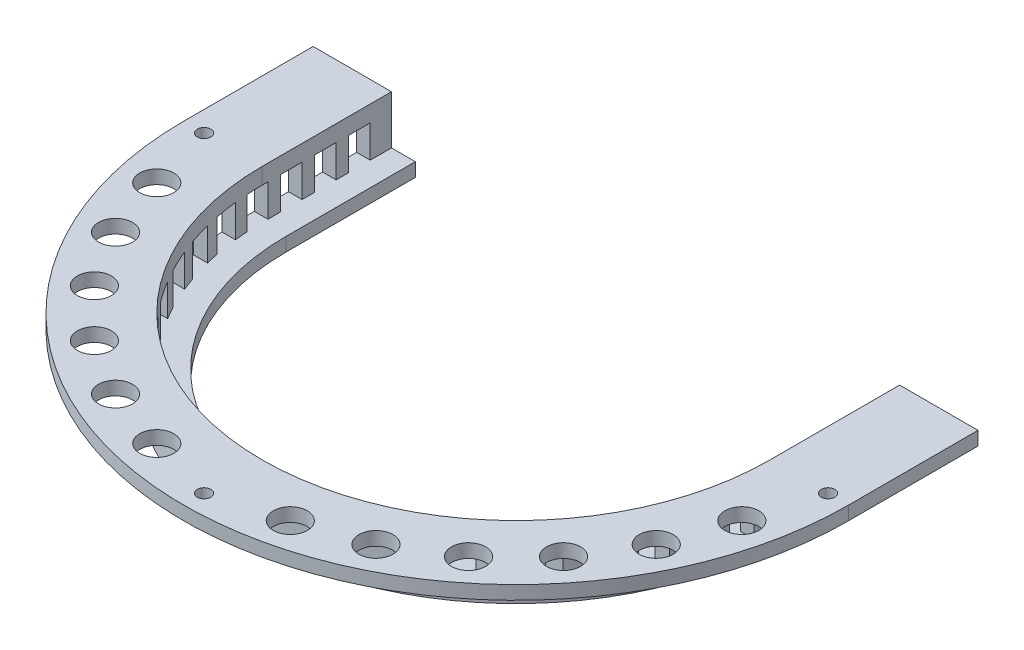
SolidWorks part; units mm, degrees
ref_plane "Front Plane" through (0, 0, 0) normal (0, 0, 1) x (1, 0, 0)
ref_plane "Top Plane" through (0, 0, 0) normal (0, 1, 0) x (1, 0, 0)
ref_plane "Right Plane" through (0, 0, 0) normal (1, 0, 0) x (0, 0, -1)
sketch "Sketch1" plane through (0, 0, 0) normal (0, 0, 1) x (1, 0, 0)
  line L0 (0, 0) -> (-74.5518, 0) construction
  line L1 (-74.5518, 0) -> (-74.5518, 14.28)
  line L2 (-74.5518, 0) -> (-67.5518, 0)
  line L3 (-67.5518, 0) -> (-67.5518, -4)
  line L4 (-67.5518, -4) -> (-78.5518, -4)
  line L5 (-78.5518, -4) -> (-78.5518, 10.28)
  line L6 (-78.5518, 14.28) -> (-74.5518, 14.28)
  line L7 (-78.5518, 14.28) -> (-97.5518, 14.28)
  line L8 (-97.5518, 14.28) -> (-97.5518, 10.28)
  line L9 (-97.5518, 10.28) -> (-78.5518, 10.28)
  line L10 (0, 0) -> (0, 25.527) construction
  dimension "D1" = 14.28
  dimension "D2" = 7
  dimension "D3" = 4
  dimension "D4" = 11
  dimension "D5" = 19
  dimension "D6" = 4
revolve "Revolve1" add sketch "Sketch1" angle 180 about L10
sketch "Sketch3" plane through (0, 0, 0) normal (0, 0, -1) x (-1, 0, 0)
  line L0 (-97.5518, 14.28) -> (-74.5518, 14.28)
  line L1 (-74.5518, 14.28) -> (-74.5518, 0)
  line L2 (-74.5518, 0) -> (-67.5518, 0)
  line L3 (-67.5518, 0) -> (-67.5518, -4)
  line L4 (-67.5518, -4) -> (-78.5518, -4)
  line L5 (-78.5518, -4) -> (-78.5518, 10.28)
  line L6 (-78.5518, 10.28) -> (-97.5518, 10.28)
  line L7 (-97.5518, 10.28) -> (-97.5518, 14.28)
extrude "Boss-Extrude1" add sketch "Sketch3" along normal blind 38
extrude "Boss-Extrude2" add sketch "Sketch1<2>" against normal blind 38
sketch "Sketch1<2>" plane through (0, 0, 0) normal (0, 0, 1) x (1, 0, 0) same geometry as "Sketch1"
ref_plane "Plane1" through (0, 10.28, 0) normal (0, -1, 0) x (-1, 0, 0)
sketch "Sketch4" plane through (0, 10.28, 0) normal (0, -1, 0) x (-1, 0, 0)
  line L0 (88.0518, 38) -> (88.0518, -43.2635) construction
  line L1 (97.5518, 38) -> (78.5518, 38) construction
  circle A0 centre (0, -91.5518) radius 2
  arc A1 (-78.5518, 0) -> (78.5518, 0) centre (0, 0) ccw construction
  circle A3 centre (-91.5518, 0) radius 2
  circle A4 centre (91.5518, 0) radius 2
  circle A6 centre (85.8442, -19.5934) radius 5
  circle A7 centre (79.332, -38.2043) radius 5
  circle A8 centre (68.8417, -54.8994) radius 5
  circle A9 centre (54.8994, -68.8417) radius 5
  circle A10 centre (38.2043, -79.332) radius 5
  circle A11 centre (19.5934, -85.8442) radius 5
  circle A13 centre (-19.5934, -85.8442) radius 5
  circle A14 centre (-38.2043, -79.332) radius 5
  circle A15 centre (-54.8994, -68.8417) radius 5
  circle A16 centre (-68.8417, -54.8994) radius 5
  circle A17 centre (-79.332, -38.2043) radius 5
  circle A18 centre (-85.8442, -19.5934) radius 5
  point P10 (0, -78.5518)
  point P49 (0, 0)
  dimension "D1" = 13
  dimension "D2" = 4
  dimension "D4" = 4
  dimension "D6" = 4
  dimension "D3" = 13
  dimension "D5" = 13
extrude "Cut-Extrude1" cut sketch "Sketch4" against normal through all
ref_plane "Plane2" through (78.5518, 0, 0) normal (1, 0, 0) x (0, 0, -1)
sketch "Sketch5" plane through (78.5518, 0, 0) normal (1, 0, 0) x (0, 0, -1)
  line L0 (0, 10.28) -> (0, -4) construction
  line L1 (25.4, 9.5) -> (31.75, 9.5)
  line L2 (25.4, 9.5) -> (25.4, 0)
  line L3 (25.4, 0) -> (31.75, 0)
  line L4 (31.75, 9.5) -> (31.75, 0)
  line L5 (38, -4) -> (0, -4) construction
  line L7 (15.4, 9.5) -> (21.75, 9.5)
  line L8 (15.4, 9.5) -> (15.4, 0)
  line L9 (15.4, 0) -> (21.75, 0)
  line L10 (21.75, 9.5) -> (21.75, 0)
  line L11 (5.4, 9.5) -> (11.75, 9.5)
  line L12 (5.4, 9.5) -> (5.4, 0)
  line L13 (5.4, 0) -> (11.75, 0)
  line L14 (11.75, 9.5) -> (11.75, 0)
  line L15 (-4.6, 9.5) -> (1.75, 9.5)
  line L16 (-4.6, 9.5) -> (-4.6, 0)
  line L17 (-4.6, 0) -> (1.75, 0)
  line L18 (1.75, 9.5) -> (1.75, 0)
  line L19 (-14.6, 9.5) -> (-8.25, 9.5)
  line L20 (-14.6, 9.5) -> (-14.6, 0)
  line L21 (-14.6, 0) -> (-8.25, 0)
  line L22 (-8.25, 9.5) -> (-8.25, 0)
  line L23 (-24.6, 9.5) -> (-18.25, 9.5)
  line L24 (-24.6, 9.5) -> (-24.6, 0)
  line L25 (-24.6, 0) -> (-18.25, 0)
  line L26 (-18.25, 9.5) -> (-18.25, 0)
  line L27 (-34.6, 9.5) -> (-28.25, 9.5)
  line L28 (-34.6, 9.5) -> (-34.6, 0)
  line L29 (-34.6, 0) -> (-28.25, 0)
  line L30 (-28.25, 9.5) -> (-28.25, 0)
  line L31 (-44.6, 9.5) -> (-38.25, 9.5)
  line L32 (-44.6, 9.5) -> (-44.6, 0)
  line L33 (-44.6, 0) -> (-38.25, 0)
  line L34 (-38.25, 9.5) -> (-38.25, 0)
  line L35 (-54.6, 9.5) -> (-48.25, 9.5)
  line L36 (-54.6, 9.5) -> (-54.6, 0)
  line L37 (-54.6, 0) -> (-48.25, 0)
  line L38 (-48.25, 9.5) -> (-48.25, 0)
  line L39 (-64.6, 9.5) -> (-58.25, 9.5)
  line L40 (-64.6, 9.5) -> (-64.6, 0)
  line L41 (-64.6, 0) -> (-58.25, 0)
  line L42 (-58.25, 9.5) -> (-58.25, 0)
  dimension "D1" = 6.35
  dimension "D2" = 25.4
  dimension "D3" = 9.5
  dimension "D4" = 4
  dimension "D5" = 10
extrude "Cut-Extrude2" cut sketch "Sketch5" against normal through all
